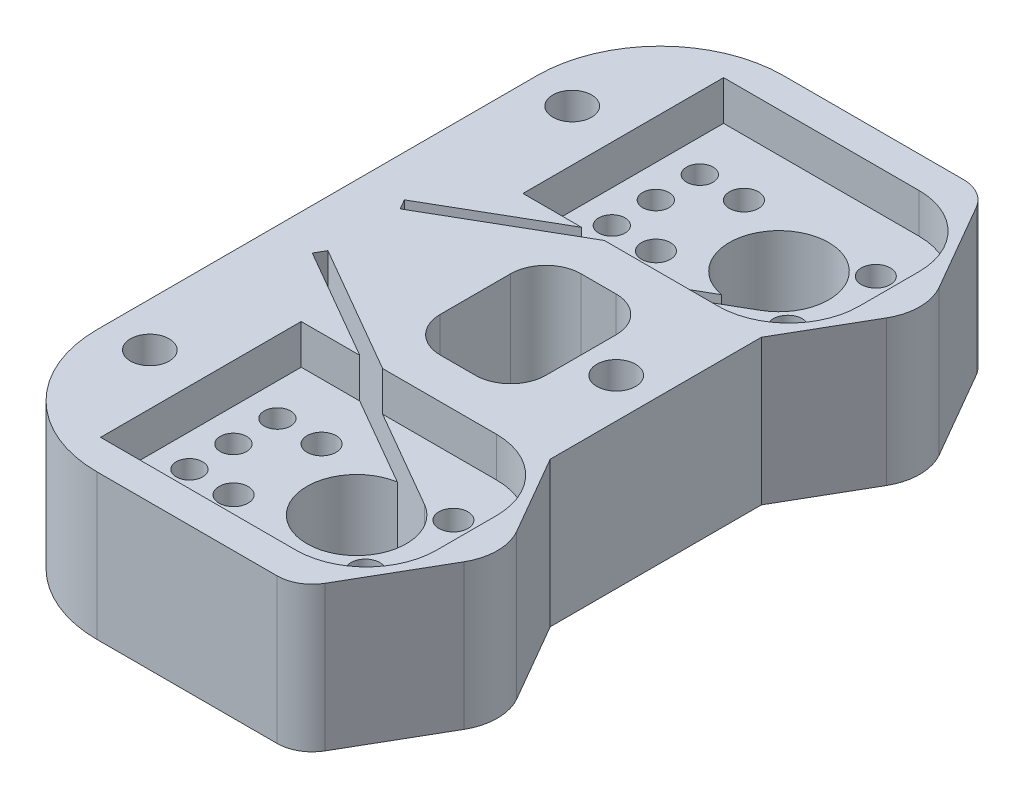
SolidWorks part; units mm, degrees
note: The reader was unsure of these and kept them because the rebuilt part matched: shared geometry of "Sketch11<4>".
material "Acrylic (Medium-high impact)"
ref_plane "Front Plane" through (0, 0, 0) normal (0, 0, 1) x (1, 0, 0)
ref_plane "Top Plane" through (0, 0, 0) normal (0, 1, 0) x (1, 0, 0)
ref_plane "Right Plane" through (0, 0, 0) normal (1, 0, 0) x (0, 0, -1)
sketch "Sketch1" plane through (0, 0, 0) normal (0, 1, 0) x (1, 0, 0)
  line L0 (32.3833, 19.5) -> (1.2064, 19.5)
  line L1 (1.2064, -19.5) -> (32.3833, -19.5)
  line L3 (21.125, 36.5896) -> (17.5, 30.3109) construction
  line L4 (0, 0) -> (17.5, -30.3109) construction
  line L5 (19.3833, -4) -> (25.3833, -4)
  line L6 (10.3833, 19.5) -> (10.3833, -19.5)
  line L7 (9.8667, 43.0896) -> (32.3833, 30.0896)
  line L9 (9.7058, 34.8109) -> (25.2942, 25.8109) construction
  line L10 (25.2942, -25.8109) -> (9.7058, -34.8109) construction
  line L11 (1.2064, 25.305) -> (1.2064, -25.305)
  line L12 (17.5, 30.3109) -> (0, 0) construction
  line L13 (19.3833, -4) -> (19.3833, 4)
  line L14 (19.3833, 4) -> (25.3833, 4)
  line L15 (0, 0) -> (26.3833, 0) construction
  line L16 (32.3833, 30.0896) -> (32.3833, -30.0896)
  line L17 (32.3833, -30.0896) -> (9.8667, -43.0896)
  line L18 (25.3833, -4) -> (25.3833, 4)
  line L19 (19.3833, -4) -> (25.3833, 4) construction
  line L20 (19.3833, 4) -> (25.3833, -4) construction
  line L23 (9.8667, 43.0896) -> (1.2064, 38.0896)
  line L24 (9.8667, -43.0896) -> (1.2064, -38.0896)
  line L25 (1.2064, 38.0896) -> (1.2064, 25.305)
  line L28 (1.2064, -38.0896) -> (1.2064, -25.305)
  line L35 (14.4288, 36.9915) -> (24.8212, 30.9915) construction
  line L69 (5.2064, -28.305) -> (5.2064, 0) construction
  line L70 (5.2064, 0) -> (5.2064, 28.305) construction
  point P4 (22.3833, 0)
  point P85 (0, 0)
  point P92 (13.1917, 0)
  point P93 (0, 0)
  point P148 (0, 0)
  dimension "D7" = 6
  dimension "D9" = 26
  dimension "D8" = 8
  dimension "D11" = 35
  dimension "D10" = 10
  dimension "D1" = 18
  dimension "D3" = 7.25
  dimension "D4" = 120
  dimension "D5" = 39
  dimension "D6" = 22
  dimension "D15" = 10
  dimension "D18" = 12
  dimension "D22" = 42.25
extrude "Boss-Extrude1" add sketch "Sketch1" along normal blind 8.25
sketch "Sketch8" plane through (0, 8.25, 0) normal (0, 1, 0) x (1, 0, 0)
  line L0 (15.7833, -6.3) -> (30.8833, -6.3)
  line L1 (15.7833, 17.7) -> (30.8833, 17.7)
  line L2 (15.7833, 17.7) -> (15.7833, 6.3)
  line L3 (15.7833, 6.3) -> (30.8833, 6.3)
  line L4 (30.8833, 17.7) -> (30.8833, 6.3)
  line L5 (32.3833, 19.5) -> (32.3833, -19.5) construction
  line L6 (32.3833, 0) -> (10.3833, 0) construction
  line L7 (10.3833, 19.5) -> (10.3833, -19.5) construction
  line L8 (30.8833, -17.7) -> (30.8833, -6.3)
  line L9 (15.7833, -17.7) -> (30.8833, -17.7)
  line L10 (15.7833, -17.7) -> (15.7833, -6.3)
  line L14 (32.3833, 19.5) -> (32.3833, -19.5) construction
  point P10 (30.8833, 12)
  dimension "D1" = 11.4
  dimension "D2" = 15.1
  dimension "D3" = 1.5
  dimension "D4" = 12
extrude "Cut-Extrude3" cut sketch "Sketch8" against normal blind 2.25
sketch "Sketch7" plane through (0, 6, 0) normal (0, 1, 0) x (1, 0, 0)
  line L1 (32.3833, 19.5) -> (32.3833, -19.5) construction
  line L4 (19.1333, 12) -> (12.8289, 12) construction
  line L5 (32.3833, 0) -> (10.3833, 0) construction
  line L7 (10.3833, 19.5) -> (10.3833, -19.5) construction
  line L8 (30.8833, 6.3) -> (30.8833, 17.7) construction
  circle A0 centre (24.6333, 12) radius 2.825
  circle A13 centre (20.1403, 14.5) radius 0.825
  circle A14 centre (27.6333, 14.5) radius 0.825
  circle A15 centre (27.6333, 9.5) radius 0.825
  circle A16 centre (20.1403, 9.5) radius 0.825
  circle A17 centre (20.1403, -9.5) radius 0.825
  circle A18 centre (27.6333, -9.5) radius 0.825
  circle A19 centre (27.6333, -14.5) radius 0.825
  circle A20 centre (20.1403, -14.5) radius 0.825
  circle A21 centre (24.6333, -12) radius 2.825
  dimension "D1" = 5.65
  dimension "D2" = 1.65
  dimension "D3" = 2
  dimension "D4" = 2
  dimension "D5" = 3
  dimension "D6" = 2.5
  dimension "D7" = 6.25
extrude "Cut-Extrude4" cut sketch "Sketch7" against normal blind 1.25
sketch "Sketch9" plane through (0, 6, 0) normal (0, 1, 0) x (1, 0, 0)
  line L0 (30.8833, 6.3) -> (30.8833, 17.7) construction
  line L1 (32.3833, 0) -> (10.3833, 0) construction
  line L2 (32.3833, 19.5) -> (32.3833, -19.5) construction
  line L3 (10.3833, 19.5) -> (10.3833, -19.5) construction
  circle A0 centre (17.6333, 14.5) radius 0.75
  circle A1 centre (20.1403, 14.5) radius 0.825 construction
  circle A3 centre (24.6333, 12) radius 2.825 construction
  circle A4 centre (17.6333, 12) radius 0.75
  circle A5 centre (17.6333, 9.5) radius 0.75
  circle A6 centre (30.1333, 12) radius 0.75
  circle A7 centre (24.6333, 12) radius 2.825 construction
  circle A8 centre (30.1333, -12) radius 0.75
  circle A9 centre (17.6333, -9.5) radius 0.75
  circle A10 centre (17.6333, -12) radius 0.75
  circle A11 centre (17.6333, -14.5) radius 0.75
  point P16 (30.8833, 12)
  dimension "D1" = 0
  dimension "D2" = 7
  dimension "D3" = 1.5
  dimension "D5" = 1.5
  dimension "D6" = 5.5
  dimension "D4" = 3
extrude "Cut-Extrude5" cut sketch "Sketch9" against normal through all
sketch "Sketch6" plane through (0, 8.25, 0) normal (0, -1, 0) x (-1, 0, 0)
  line L0 (0, 0) -> (32.3833, 0) construction
  line L1 (-26.0458, -9.5535) -> (-25.7208, -10.1164)
  line L2 (-12.7304, -2.6164) -> (-25.7208, -10.1164)
  line L3 (-13.0554, -2.0535) -> (-26.0458, -9.5535)
  line L4 (-13.0554, -2.0535) -> (-12.7304, -2.6164)
  line L5 (-13.0554, 2.0535) -> (-12.7304, 2.6164)
  line L6 (-32.3833, 19.5) -> (-32.3833, -19.5) construction
  line L7 (-13.0554, 2.0535) -> (-26.0458, 9.5535)
  line L8 (-12.7304, 2.6164) -> (-25.7208, 10.1164)
  line L9 (-26.0458, 9.5535) -> (-25.7208, 10.1164)
  circle A0 centre (-24.6333, -12) radius 2.825
  circle A1 centre (-24.6333, -12) radius 2.825 construction
  circle A2 centre (-24.6333, 12) radius 2.825
  dimension "D1" = 5.65
  dimension "D2" = 15
  dimension "D3" = 60
  dimension "D4" = 0.65
extrude "Cut-Extrude1" cut sketch "Sketch6" along normal through all both and the other way through all from surface at 2.25
sketch "Sketch11" plane through (0, 8.25, 0) normal (0, 1, 0) x (1, 0, 0)
  line L0 (29.6333, 3.8625) -> (29.6333, 22.3095) construction
  line L1 (32.2314, 13.5) -> (28.7673, 19.5)
  line L2 (32.2314, 10.5) -> (29.6333, 6)
  line L3 (29.6333, 12) -> (29.6333, 18)
  line L4 (29.6333, 12) -> (29.6333, 6)
  line L5 (32.3833, 0) -> (10.3833, 0) construction
  line L6 (32.3833, 19.5) -> (32.3833, -19.5) construction
  line L7 (10.3833, 19.5) -> (10.3833, -19.5) construction
  line L8 (29.6333, 6) -> (29.6333, -6)
  line L9 (32.3833, -19.5) -> (23.5715, -19.5) construction
  line L10 (29.6333, -3.8625) -> (29.6333, -22.3095) construction
  line L11 (29.6333, -12) -> (29.6333, -6)
  line L12 (29.6333, -12) -> (29.6333, -18)
  line L13 (32.3833, 19.5) -> (23.5715, 19.5) construction
  line L14 (32.3833, 19.5) -> (10.3833, 19.5) construction
  line L15 (32.2314, -10.5) -> (29.6333, -6)
  line L16 (32.2314, -13.5) -> (28.7673, -19.5)
  arc A0 (29.6333, 9) -> (29.6333, 15) centre (29.6333, 12) ccw
  arc A1 (26.0458, 9.5535) -> (24.1596, 9.215) centre (24.6333, 12) ccw construction
  arc A2 (29.6333, -9) -> (29.6333, -15) centre (29.6333, -12) cw
  point P20 (29.6333, 0)
  line M28 (32.3833, -19.5) -> (32.3833, 19.5)
  dimension "D1" = 5
  dimension "D2" = 0
  dimension "D3" = 6
  dimension "D4" = 6
  dimension "D5" = 6
extrude "Boss-Extrude2" add sketch "Sketch11" against normal through all contours A0 M28 | A2 M28
fillet "Fillet3" radius 4 4 edges at (30.8833, 7.125, 17.7) (30.8833, 7.125, 6.3) (30.8833, 7.125, -6.3) (30.8833, 7.125, -17.7)
fillet "Fillet4" radius 2 4 edges at (25.3833, 4.125, -4) (19.3833, 4.125, 4) (25.3833, 4.125, 4) (19.3833, 4.125, -4)
extrude "Cut-Extrude7" cut sketch "Sketch11<4>" against normal through all
sketch "Sketch11<4>" plane through (0, 8.25, 0) normal (0, 1, 0) x (1, 0, 0) same geometry as "Sketch11"
fillet "Fillet5" radius 7 2 edges at (10.3833, 4.125, 19.5) (10.3833, 4.125, -19.5)
sketch "Sketch12" plane through (0, 8.25, 0) normal (0, 1, 0) x (1, 0, 0)
  line L0 (12.8833, 12) -> (12.8833, -12) construction
  line L1 (10.3833, 12.5) -> (10.3833, -12.5) construction
  line L2 (12.8833, 0) -> (27.3833, 0) construction
  line L3 (29.6333, 6) -> (29.6333, -6) construction
  point P4 (10.3833, 0)
  point P5 (12.8833, 0)
  dimension "D1" = 24
  dimension "D2" = 14.5
  dimension "D3" = 2.25
hole_wizard "Ø2.2 (2.2) Diameter Hole1" positions "3DSketch1" profile "Sketch13" hole size "Ø2.2" standard "ISO" end condition through all
sketch3d "3DSketch1"
  point P0 (12.8833, 8.25, -12)
  point P3 (27.3833, 8.25, 0)
  point P6 (12.8833, 8.25, 12)
sketch "Sketch13" plane through (12.8833, 8.25, -12) normal (1, 0, 0) x (0, 0, 1)
  line L0 (0, 0) -> (0, 8.25)
  line L1 (0, 8.25) -> (1.1, 8.25)
  line L2 (1.1, 8.25) -> (1.1, 0)
  line L5 (1.1, 0) -> (0, 0)
  line L11 (0, -6.35) -> (0, 107.95) construction
  dimension "Thru Hole Dia." = 2.2
  dimension "Thru Hole Depth" = 8.25
fillet "Fillet6" radius 2 2 edges at (28.7673, 4.125, 19.5) (28.7673, 4.125, -19.5)
